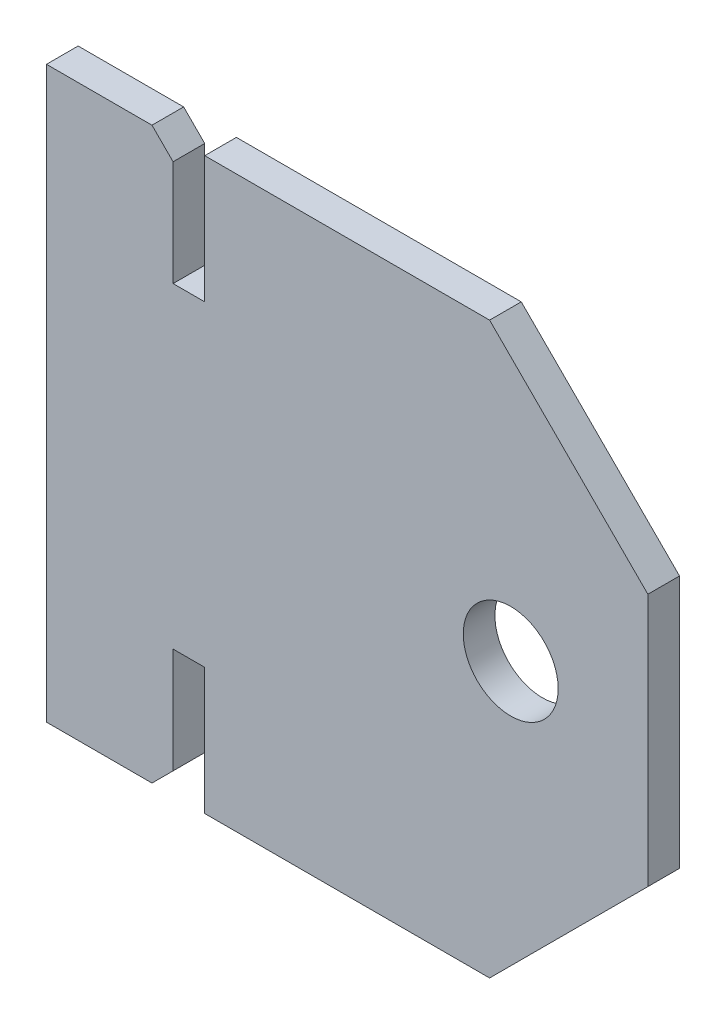
SolidWorks part; units mm, degrees
note: The reader was unsure of these and kept them because the rebuilt part matched: thickness of "Base-Flange1", "Sheet-Metal1", "Sheet-Metal2", "Sheet-Metal3".
material "AISI 304"
ref_plane "Front Plane" through (0, 0, 0) normal (0, 0, 1) x (1, 0, 0)
ref_plane "Top Plane" through (0, 0, 0) normal (0, 1, 0) x (1, 0, 0)
ref_plane "Right Plane" through (0, 0, 0) normal (1, 0, 0) x (0, 0, -1)
sketch "Sketch1" plane through (0, 0, 0) normal (0, 0, 1) x (1, 0, 0)
  line L0 (-5.3228, 29.0584) -> (23.6772, 29.0584)
  line L1 (-20.3228, -24.9416) -> (-8.3228, -24.9416)
  line L2 (-20.3228, -24.9416) -> (-20.3228, 29.0584)
  line L3 (-20.3228, 29.0584) -> (-8.3228, 29.0584)
  line L5 (-20.3228, -24.9416) -> (23.6772, 29.0584) construction
  line L6 (-20.3228, 29.0584) -> (17.4436, -24.9416) construction
  line L8 (-8.3228, 29.0584) -> (-8.3228, 17.0584)
  line L9 (-8.3228, 17.0584) -> (-5.3228, 17.0584)
  line L10 (-5.3228, 29.0584) -> (-5.3228, 17.0584)
  line L12 (-8.3228, -24.9416) -> (-8.3228, -12.9416)
  line L13 (-8.3228, -12.9416) -> (-5.3228, -12.9416)
  line L14 (-5.3228, -24.9416) -> (-5.3228, -12.9416)
  line L15 (-5.3228, -24.9416) -> (17.4436, -24.9416)
  line L16 (23.6772, 29.0584) -> (36.6772, 29.0584)
  line L17 (36.6772, 29.0584) -> (36.6772, -24.9416)
  line L18 (36.6772, -24.9416) -> (17.4436, -24.9416)
  circle A1 centre (23.6772, 2.0584) radius 4.5
  point P0 (0, 0)
  dimension "D3" = 9
  dimension "D4" = 12
  dimension "D2" = 12
  dimension "D1" = 54
  dimension "D5" = 3
  dimension "D6" = 29
  dimension "D7" = 13
base flange "Base-Flange1" sketch "Sketch1" thickness 3 reverse thickness direction no parameters "D1"=2.5
sketch "Sketch6" [suppressed] plane through (0, 0, 0) normal (0, 0, 1) x (1, 0, 0)
  line L0 (33.25, 27) -> (-33.25, 27) construction
  line L1 (0.75, 27) -> (3.75, 27)
  line L2 (0.75, 27) -> (0.75, 13)
  line L3 (0.75, 13) -> (3.75, 13)
  line L4 (3.75, 27) -> (3.75, 13)
  line L5 (-33.25, 27) -> (-33.25, -27) construction
  dimension "D1" = 3
  dimension "D2" = 14
  dimension "D3" = 34
extrude "Cut-Extrude1" [suppressed] cut sketch "Sketch6" against normal blind 10
mirror "Mirror1" [suppressed] about plane through (0, 0, 0) normal (0, 1, 0)
chamfer "Chamfer1" [suppressed] distance 2 angle 45
chamfer "Chamfer2" distance 15 angle 45 2 edges at (36.6772, -24.9416, -1.5) (36.6772, 29.0584, -1.5)
chamfer "Chamfer3" distance 2 angle 45 2 edges at (-8.3228, 29.0584, -1.5) (-8.3228, -24.9416, -1.5)
sketch "Bend-Lines1" [suppressed] plane through (0, 0, 0) normal (0, 1, 0) x (1, 0, 0)
sketch "Bounding-Box1" [suppressed] plane through (0, 0, 0) normal (0, 1, 0) x (1, 0, 0)
sheet metal parameters "Sheet-Metal1" thickness 3 parameters "D1"=2.5
flat pattern "Flat-Pattern1" [suppressed]
sketch "Bend-Lines2" plane through (0, 0, 0) normal (0, 1, 0) x (1, 0, 0)
sketch3d "Bounding-Box2" [suppressed]
  line L0 (-20.3228, -24.9416, 0) -> (36.6772, -24.9416, 0) construction
  line L1 (-20.3228, 29.0584, 0) -> (36.6772, 29.0584, 0) construction
  line L2 (-20.3228, -24.9416, 0) -> (-20.3228, 29.0584, 0) construction
  line L3 (36.6772, -24.9416, 0) -> (36.6772, 29.0584, 0) construction
sheet metal parameters "Sheet-Metal2" thickness 3 parameters "D1"=2.5, "D7"=2
flat pattern "Flat-Pattern1"
sketch "Bend-Lines2" plane through (0, 0, 0) normal (0, 1, 0) x (1, 0, 0)
sketch3d "Bounding-Box2" [suppressed]
  line L0 (-70, -17, 0) -> (17, -17, 0) construction
  line L1 (-70, 17, 0) -> (17, 17, 0) construction
  line L2 (-70, -17, 0) -> (-70, 17, 0) construction
  line L3 (17, -17, 0) -> (17, 17, 0) construction
sheet metal parameters "Sheet-Metal3" thickness 3 parameters "D1"=2.5, "D7"=2
flat pattern "Flat-Pattern1"
sketch "Bend-Lines2" plane through (0, 0, 0) normal (0, 1, 0) x (1, 0, 0)
sketch3d "Bounding-Box2" [suppressed]
  line L0 (-66.5, -27, 0) -> (27, -27, 0) construction
  line L1 (-66.5, 27, 0) -> (27, 27, 0) construction
  line L2 (-66.5, -27, 0) -> (-66.5, 27, 0) construction
  line L3 (27, -27, 0) -> (27, 27, 0) construction
